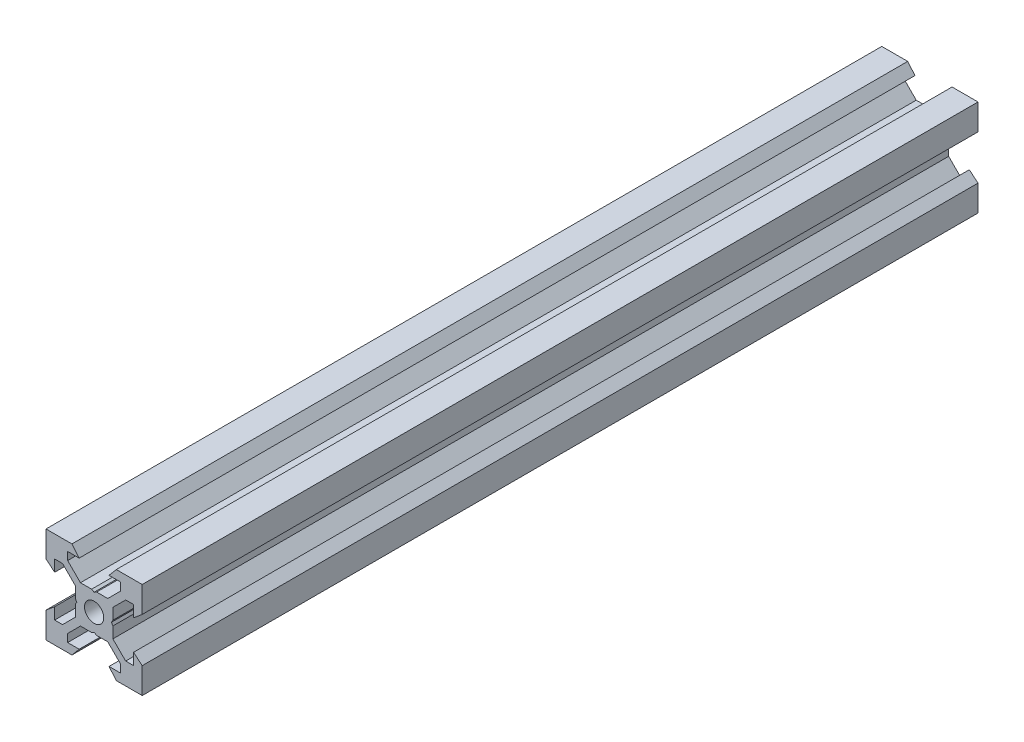
SolidWorks part; units mm, degrees
ref_plane "Front Plane" through (0, 0, 0) normal (0, 0, 1) x (1, 0, 0)
ref_plane "Top Plane" through (0, 0, 0) normal (0, 1, 0) x (1, 0, 0)
ref_plane "Right Plane" through (0, 0, 0) normal (1, 0, 0) x (0, 0, -1)
sketch "Sketch1" plane through (0, 0, 0) normal (0, 0, 1) x (1, 0, 0)
  line L0 (10, 10) -> (4.6104, 10) construction
  line L1 (10, 10) -> (10, 4.6104) construction
  line L2 (10, -10) -> (10, -4.6104) construction
  line L3 (10, -10) -> (4.6104, -10) construction
  line L4 (10, 10) -> (10, 4.6104)
  line L5 (6.5607, 5.5) -> (8.2, 5.5)
  line L6 (5.5, 8.2) -> (5.5, 6.5607)
  line L7 (10, 10) -> (4.6104, 10)
  line L8 (10, 10) -> (10, 4.6104)
  line L9 (6.5607, 5.5) -> (3.9, 2.8393)
  line L10 (5.5, 6.5607) -> (2.8393, 3.9)
  line L11 (10, 4.6104) -> (8.2, 3.1)
  line L12 (4.6104, 10) -> (3.1, 8.2)
  line L13 (8.2, 3.1) -> (8.2, 5.5)
  line L14 (3.1, 8.2) -> (5.5, 8.2)
  line L15 (-6.5607, 5.5) -> (-8.2, 5.5)
  line L16 (6.5607, -5.5) -> (8.2, -5.5)
  line L17 (3.1, -8.2) -> (5.5, -8.2)
  line L18 (8.2, -3.1) -> (8.2, -5.5)
  line L19 (4.6104, -10) -> (3.1, -8.2)
  line L20 (10, -4.6104) -> (8.2, -3.1)
  line L21 (0.5196, -3.9) -> (0, -3.6)
  line L22 (0.5196, 3.9) -> (0, 3.6)
  line L23 (3.6, 0) -> (3.9, -0.5196)
  line L24 (3.9, 0.5196) -> (3.6, 0)
  line L25 (3.9, 0.5196) -> (3.9, 2.8393)
  line L26 (2.8393, 3.9) -> (0.5196, 3.9)
  line L27 (3.9, -2.8393) -> (3.9, -0.5196)
  line L28 (2.8393, -3.9) -> (0.5196, -3.9)
  line L29 (5.5, -6.5607) -> (2.8393, -3.9)
  line L30 (6.5607, -5.5) -> (3.9, -2.8393)
  line L31 (10, -10) -> (10, -4.6104)
  line L32 (10, -10) -> (4.6104, -10)
  line L33 (5.5, -8.2) -> (5.5, -6.5607)
  line L34 (-6.5607, -5.5) -> (-8.2, -5.5)
  line L35 (10, -10) -> (10, -4.6104)
  line L36 (0, 0) -> (0, 8.2) construction
  line L37 (-10, -10) -> (-4.6104, -10) construction
  line L38 (-10, -10) -> (-10, -4.6104) construction
  line L39 (-10, 10) -> (-10, 4.6104) construction
  line L40 (-10, 10) -> (-4.6104, 10) construction
  line L41 (-10, -10) -> (-10, -4.6104)
  line L43 (-5.5, -8.2) -> (-5.5, -6.5607)
  line L44 (-10, -10) -> (-4.6104, -10)
  line L45 (-10, -10) -> (-10, -4.6104)
  line L46 (-6.5607, -5.5) -> (-3.9, -2.8393)
  line L47 (-5.5, -6.5607) -> (-2.8393, -3.9)
  line L48 (-2.8393, -3.9) -> (-0.5196, -3.9)
  line L49 (-3.9, -2.8393) -> (-3.9, -0.5196)
  line L50 (-2.8393, 3.9) -> (-0.5196, 3.9)
  line L51 (-3.9, 0.5196) -> (-3.9, 2.8393)
  line L52 (-3.9, 0.5196) -> (-3.6, 0)
  line L53 (-3.6, 0) -> (-3.9, -0.5196)
  line L54 (-0.5196, 3.9) -> (0, 3.6)
  line L55 (-0.5196, -3.9) -> (0, -3.6)
  line L56 (-10, -4.6104) -> (-8.2, -3.1)
  line L57 (-4.6104, -10) -> (-3.1, -8.2)
  line L58 (-8.2, -3.1) -> (-8.2, -5.5)
  line L59 (-3.1, -8.2) -> (-5.5, -8.2)
  line L60 (-10, -10) -> (10, -10) construction
  line L61 (-10, -10) -> (-10, 10) construction
  line L62 (-3.1, 8.2) -> (-5.5, 8.2)
  line L63 (-8.2, 3.1) -> (-8.2, 5.5)
  line L64 (-4.6104, 10) -> (-3.1, 8.2)
  line L65 (-10, 4.6104) -> (-8.2, 3.1)
  line L66 (-5.5, 6.5607) -> (-2.8393, 3.9)
  line L67 (-6.5607, 5.5) -> (-3.9, 2.8393)
  line L68 (-10, 10) -> (-10, 4.6104)
  line L69 (-10, 10) -> (-4.6104, 10)
  line L70 (-5.5, 8.2) -> (-5.5, 6.5607)
  line L71 (-10, 10) -> (10, 10) construction
  line L72 (-10, 10) -> (-10, 4.6104)
  line L73 (10, -10) -> (10, 10) construction
  line L74 (-10, -10) -> (10, 10) construction
  line L75 (-10, 10) -> (10, -10) construction
  circle A0 centre (0, 0) radius 2
  dimension "D7" = 4
  dimension "D1" = 20
  dimension "D2" = 5.3896
  dimension "D3" = 4.5
  dimension "D4" = 50
  dimension "D5" = 1.8
  dimension "D6" = 1.5104
  dimension "D8" = 5.5
  dimension "D9" = 120
  dimension "D10" = 0.3
  dimension "D11" = 2.3197
  dimension "D12" = 7.8
  dimension "D13" = 7.8
  dimension "D14" = 1.5
  dimension "D15" = 2.6607
extrude "Boss-Extrude1" add sketch "Sketch1" along normal mid plane 173.74 contours L70 L62 L64 L69 L68 L65 L63 L15 L67 L51 L52 L53 L49 L46 L34 L58 L56 L41 L44 L57 L59 L43 L47 L48 L55 L21 L28 L29 L33 L17 L19 L32 L31 L20 L18 L16 L30 L27 L23 L24 L25 L9 L5 L13 L11 L4 L7 L12 L14 L6 L10 region at (9.7172, 7.3052, 0)
